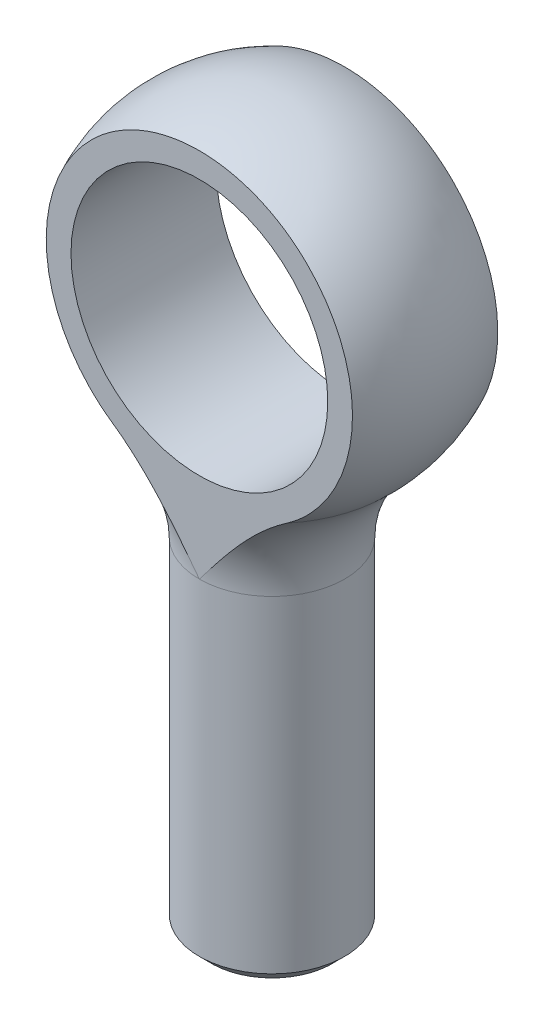
SolidWorks part; units mm, degrees
ref_plane "Front" through (0, 0, 0) normal (0, 0, 1) x (1, 0, 0)
ref_plane "Top" through (0, 0, 0) normal (0, 1, 0) x (1, 0, 0)
ref_plane "Right" through (0, 0, 0) normal (1, 0, 0) x (0, 0, -1)
sketch "Sketch1" plane through (0, 0, 0) normal (0, 0, 1) x (1, 0, 0)
  line L0 (0, 0) -> (0, -44.45)
  line L1 (0, -44.45) -> (9.525, -44.45)
  line L2 (9.525, -44.45) -> (9.525, 0)
  line L3 (9.525, 0) -> (0, 0)
  line L5 (0, 50.8) -> (0, 0) construction
  line L6 (0, 50.8) -> (22.225, 50.8) construction
  line L7 (22.225, 50.8) -> (22.225, 28.575) construction
  line L8 (-9.525, -44.45) -> (-9.525, 0) construction
  arc A0 (14.893, 12.0781) -> (0, 50.8) centre (0, 28.575) ccw construction
  circle A1 centre (0, 28.575) radius 9.525 construction
  circle A2 centre (0, 28.575) radius 16.6687 construction
  circle A3 centre (0, 28.575) radius 16.8354 construction
  arc A4 (9.525, 0) -> (14.893, 12.0781) centre (25.7969, 0) cw construction
  dimension "A" = 19.05
  dimension "Ball Dia" = 33.3375
  dimension "B" = 44.45
  dimension "D1" = 33.6709
  dimension "D" = 73.025
  dimension "E" = 44.45
  dimension "Thread Dia" = 19.05
revolve "Revolve1" add sketch "Sketch1" angle 360 about L5
cosmetic thread "Cosmetic Thread9" parameters "D2"=17.178
chamfer "Chamfer2" distance 1.5875 angle 45 1 edges at (-9.525, -44.45, 0)
sketch "Sketch12" plane through (0, -44.45, 0) normal (0, -1, 0) x (1, 0, 0)
  circle A1 centre (0, 0) radius 7.9375
  circle A2 centre (0, 0) radius 7.9375
  dimension "D1" = 0
curve "Helix/Spiral1" [suppressed] pitch 1.5875 height 49.53 turns 31.2
sketch "Sketch13" plane through (0, 0, 0) normal (0, 0, 1) x (1, 0, 0)
  line L0 (9.525, -44.45) -> (9.525, -45.8391)
  line L1 (9.525, -45.8391) -> (8.4939, -45.2437)
  line L2 (8.4939, -45.2437) -> (8.4939, -45.0453)
  line L3 (8.4939, -45.0453) -> (9.525, -44.45)
  line L4 (9.0094, -44.7477) -> (9.0094, -45.5414) construction
  dimension "D1" = 60
  dimension "D2" = 0.1984
  dimension "D3" = 0.7937
sweep "Cut-Sweep2" [suppressed] cut profiles "Sketch13" path "Helix/Spiral1"
sketch "Sketch4" plane through (0, 0, 0) normal (0, 0, 1) x (1, 0, 0)
  line L0 (9.525, 0) -> (0, 0) construction
  line L2 (0, 50.8) -> (0, 0) construction
  line L3 (9.525, 0) -> (0, 0)
  line L5 (0, 50.8) -> (0, 0)
  line L6 (0, 50.8) -> (0, 53.34) construction
  arc A0 (14.893, 12.0781) -> (0, 50.8) centre (0, 28.575) ccw construction
  arc A1 (14.893, 12.0781) -> (0, 50.8) centre (0, 28.575) ccw
  arc A2 (14.893, 12.0781) -> (9.525, 0) centre (25.7969, 0) ccw construction
  arc A3 (14.893, 12.0781) -> (9.525, 0) centre (25.7969, 0) ccw
  dimension "D1" = 2.54
revolve "Revolve2" add sketch "Sketch4" angle 360 about L6
sketch "Sketch5" plane through (0, 0, 0) normal (1, 0, 0) x (0, 0, -1)
  line L0 (9.525, 50.8) -> (22.225, 50.8)
  line L1 (-9.525, 50.8) -> (9.525, 50.8) construction
  line L2 (-9.525, 50.8) -> (-9.525, 0)
  line L3 (-9.525, 0) -> (9.525, 0) construction
  line L4 (9.525, 50.8) -> (9.525, 0)
  line L5 (22.225, 50.8) -> (22.225, 0)
  line L6 (22.225, 0) -> (9.525, 0)
  line L7 (-9.525, 0) -> (-22.225, 0)
  line L8 (-22.225, 0) -> (-22.225, 50.8)
  line L9 (-22.225, 50.8) -> (-9.525, 50.8)
  line L13 (0, 0) -> (0, 3.0162) construction
  arc A0 (14.893, 12.0781) -> (-14.893, 12.0781) centre (0, 28.575) ccw construction
  dimension "D1" = 19.05
extrude "Cut-Extrude1" cut sketch "Sketch5" against normal through all and the other way through all
sketch "Sketch6" plane through (0, 0, 0) normal (0, 0, 1) x (1, 0, 0)
  circle A0 centre (0, 28.575) radius 16.8354 construction
  circle A1 centre (0, 28.575) radius 16.8354
extrude "Cut-Extrude2" cut sketch "Sketch6" against normal through all and the other way through all
sketch "Sketch7" plane through (0, 0, 0) normal (0, 0, 1) x (1, 0, 0)
  line L0 (0, 45.2437) -> (0, 11.9062)
  line L1 (0, 50.8) -> (0, 0) construction
  line L2 (0, 0) -> (0, 11.9062) construction
  arc A0 (0, 11.9062) -> (0, 45.2437) centre (0, 28.575) ccw
  circle A1 centre (0, 28.575) radius 16.6687 construction
revolve "Revolve3" add sketch "Sketch7" angle 360 about L2
sketch "Sketch8" plane through (0, 0, 0) normal (1, 0, 0) x (0, 0, -1)
  line L0 (-9.525, 50.8) -> (9.525, 50.8) construction
  line L1 (-11.1125, 50.8) -> (11.1125, 50.8) construction
  line L2 (-11.1125, 50.8) -> (-11.1125, 0)
  line L3 (-11.1125, 0) -> (11.1125, 0) construction
  line L4 (11.1125, 50.8) -> (11.1125, 0)
  line L5 (11.1125, 50.8) -> (22.225, 50.8)
  line L6 (22.225, 50.8) -> (22.225, 0)
  line L7 (22.225, 0) -> (11.1125, 0)
  line L8 (-11.1125, 0) -> (-22.225, 0)
  line L9 (-22.225, 0) -> (-22.225, 50.8)
  line L10 (-22.225, 50.8) -> (-11.1125, 50.8)
  dimension "C" = 22.225
extrude "Cut-Extrude3" cut sketch "Sketch8" against normal through all and the other way through all
sketch "Sketch10" plane through (0, 0, 0) normal (0, 0, 1) x (1, 0, 0)
  circle A0 centre (0, 28.575) radius 9.525 construction
  circle A1 centre (0, 28.575) radius 9.525
extrude "Cut-Extrude4" cut sketch "Sketch10" against normal through all and the other way through all
chamfer "Chamfer1" distance 0.9525 angle 45 2 edges at (9.525, 28.575, -11.1125) (9.525, 28.575, 11.1125)
sketch "Sketch14" [suppressed] plane through (0, 0, 0) normal (1, 0, 0) x (0, 0, -1)
  line L0 (2.4016, 13.0969) -> (-2.4016, 13.0969) construction
  line L1 (3.9688, 13.0969) -> (-3.9688, 13.0969)
  line L2 (-3.9688, 13.0969) -> (-3.9688, 13.6049)
  line L3 (-2.6, 13.5616) -> (2.6, 13.5616)
  line L4 (-2.6, 13.5616) -> (-2.6, 8.6634) construction
  line L5 (3.9688, 13.6049) -> (3.9688, 13.0969)
  arc A0 (-3.9688, 13.6049) -> (-2.6, 13.5616) centre (-3.9688, -8.0834) cw
  arc A1 (2.6, 13.5616) -> (3.9688, 13.6049) centre (3.9688, -8.0834) cw
  point P11 (0, 13.0969)
  dimension "D1" = 7.9375
  dimension "D2" = 0.508
revolve "Revolve4" [suppressed] add sketch "Sketch14" angle 360
fillet "Fillet1" [suppressed] radius 0.508
sketch "Sketch11" plane through (0, 0, 0) normal (1, 0, 0) x (0, 0, -1)
  line L0 (0, 28.575) -> (-11.1125, 30.937) construction
  line L1 (9.525, 28.575) -> (-9.525, 28.575) construction
  line L2 (0, 28.575) -> (-11.1125, 26.213) construction
  line L3 (0, 50.8) -> (0, 0) construction
  line L4 (-11.1125, 50.8) -> (-11.1125, 0) construction
  line L5 (0, 28.575) -> (0.0074, 28.575) construction
  dimension "Swivel" = 24
sketch "Sketch15" plane through (0, 0, 0) normal (1, 0, 0) x (0, 0, -1)
  line L0 (-10.16, 19.05) -> (10.16, 19.05) construction
  line L1 (10.16, 38.1) -> (-10.16, 38.1) construction
  line L2 (-10.16, 19.05) -> (10.16, 19.05) construction
  line L3 (10.16, 38.1) -> (-10.16, 38.1) construction
  line L4 (-9.525, 48.6555) -> (-9.525, 12.0781) construction
  line L5 (9.525, 12.0781) -> (9.525, 48.6555) construction
  arc A0 (-11.1125, 16.1508) -> (11.1125, 16.1508) centre (0, 28.575) ccw construction
  arc A1 (11.1125, 40.9992) -> (-11.1125, 40.9992) centre (0, 28.575) ccw construction
  arc A2 (-9.525, 14.8958) -> (9.525, 14.8958) centre (0, 28.575) ccw construction
  arc A3 (9.525, 42.2542) -> (-9.525, 42.2542) centre (0, 28.575) ccw construction
delete or keep bodies "Body-Delete/Keep 1" type delete bodies bodies 116
ref_plane "Plane1" through (0, 0, 0) normal (0, 1, 0) x (1, 0, 0)
ref_plane "Plane2" through (0, -42.8625, 0) normal (0, 1, 0) x (1, 0, 0)
equation "\"D1@Sketch1\"=\"Ball Dia@Sketch1\"*1.01"
equation "\"D1@Chamfer1\"=\"A@Sketch1\"/20"
equation "\"D1@Sketch5\"=\"Thread Dia@Sketch1\""
equation "\"D3@Helix/Spiral1\" = \"E@Sketch1\" + .2"
equation "\"D2@Sketch13\" = \"D4@Helix/Spiral1\" * .125"
equation "\"D3@Sketch13\" = \"D4@Helix/Spiral1\" * .5"
equation "\"D1@Chamfer2\" = \"D4@Helix/Spiral1\" * 1"
